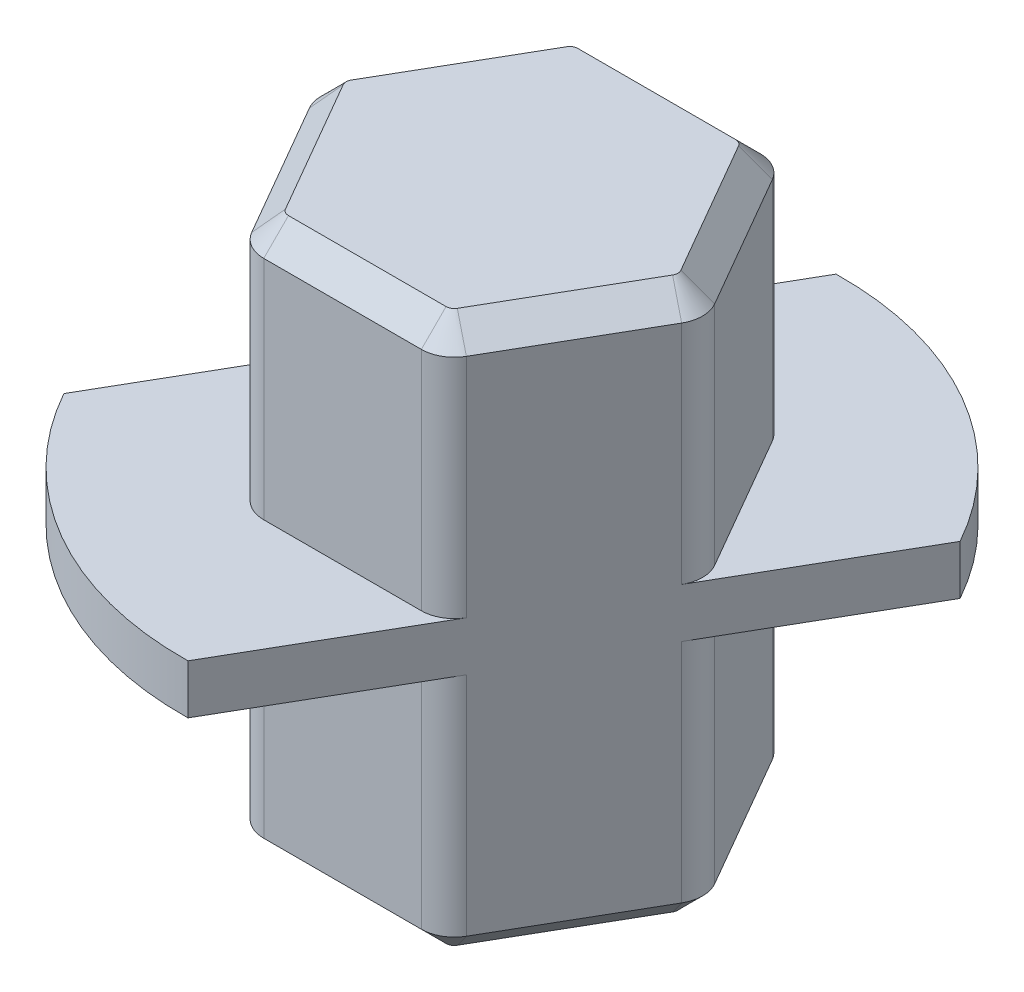
SolidWorks part; units mm, degrees
ref_plane "Front Plane" through (0, 0, 0) normal (0, 0, 1) x (1, 0, 0)
ref_plane "Top Plane" through (0, 0, 0) normal (0, 1, 0) x (1, 0, 0)
ref_plane "Right Plane" through (0, 0, 0) normal (1, 0, 0) x (0, 0, -1)
sketch "Sketch1" plane through (0, 0, 0) normal (0, 1, 0) x (1, 0, 0)
  line L0 (-11.875, 0) -> (11.875, 0) construction
  line L7 (5.9375, 10.2841) -> (-5.9375, 10.2841)
  line L8 (-5.9375, 10.2841) -> (-11.875, 0)
  line L9 (-11.875, 0) -> (-5.9375, -10.2841)
  line L10 (-5.9375, -10.2841) -> (5.9375, -10.2841)
  line L11 (5.9375, -10.2841) -> (11.875, 0)
  line L12 (11.875, 0) -> (5.9375, 10.2841)
  line L13 (-5.9375, -10.2841) -> (5.9375, 10.2841) construction
  circle A0 centre (0, 0) radius 10.2841 construction
  dimension "D1" = 23.75
extrude "Boss-Extrude1" add sketch "Sketch1" along normal blind 15.24
sketch "Sketch2" plane through (0, 15.24, 0) normal (0, 1, 0) x (1, 0, 0)
  circle A0 centre (0, 0) radius 20
  dimension "D1" = 40
extrude "Boss-Extrude2" add sketch "Sketch2" along normal blind 3
extrude "Boss-Extrude3" add sketch "Sketch1<2>" along normal blind 15.24 from surface starting at face at (0, 18.24, 20)
sketch "Sketch1<2>" plane through (0, 0, 0) normal (0, 1, 0) x (1, 0, 0) same geometry as "Sketch1"
fillet "Fillet1" radius 2 12 edges at (5.9375, 7.62, -10.2841) (-5.9375, 7.62, -10.2841) (-11.875, 7.62, 0) (-5.9375, 7.62, 10.2841) (5.9375, 7.62, 10.2841) (11.875, 7.62, 0) (5.9375, 25.86, -10.2841) (-5.9375, 25.86, -10.2841) (-11.875, 25.86, 0) (-5.9375, 25.86, 10.2841) (5.9375, 25.86, 10.2841) (11.875, 25.86, 0)
sketch "Sketch3" plane through (-8.9063, 0, -5.142) normal (-0.866, 0, -0.5) x (-0.5, 0, 0.866)
  line L1 (-17.3683, 33.4435) -> (18.5213, 33.4435)
  line L2 (-17.3683, 33.4435) -> (-17.3683, 12.0694)
  line L3 (-17.3683, 12.0694) -> (18.5213, 12.0694)
  line L4 (18.5213, 33.4435) -> (18.5213, 12.0694)
extrude "Cut-Extrude1" cut sketch "Sketch3" along normal through all
chamfer "Chamfer2" distance 1.5 angle 45 24 edges at (-5.7828, 0, -10.0161) (-8.9062, 0, -5.142) (-11.5656, 0, 0) (-8.9063, 0, 5.142) (-5.7828, 0, 10.0161) (0, 0, 10.2841) (5.7828, 0, 10.0161) (8.9063, 0, 5.142) (11.5656, 0, 0) (8.9063, 0, -5.142) (5.7828, 0, -10.0161) (0, 0, -10.2841) (11.5656, 33.48, 0) (8.9063, 33.48, 5.142) (5.7828, 33.48, 10.0161) (0, 33.48, 10.2841) (-5.7828, 33.48, 10.0161) (-8.9063, 33.48, 5.142) (-11.5656, 33.48, 0) (-8.9063, 33.48, -5.142) (-5.7828, 33.48, -10.0161) (0, 33.48, -10.2841) (5.7828, 33.48, -10.0161) (8.9063, 33.48, -5.142)
sketch "Sketch5" plane through (8.9063, 0, 5.142) normal (0.866, 0, 0.5) x (0.5, 0, -0.866)
  line L1 (-26.761, 28.7725) -> (24.6789, 28.7725)
  line L2 (-26.761, 28.7725) -> (-26.761, 12.8455)
  line L3 (-26.761, 12.8455) -> (24.6789, 12.8455)
  line L4 (24.6789, 28.7725) -> (24.6789, 12.8455)
extrude "Cut-Extrude3" cut sketch "Sketch5" along normal through all
sketch "Sketch4" plane through (0, 33.48, 0) normal (0, 1, 0) x (1, 0, 0)
  line L1 (3.6281, 6.2841) -> (-3.6281, 6.2841)
  line L2 (-3.6281, 6.2841) -> (-7.2562, 0)
  line L3 (-7.2562, 0) -> (-3.6281, -6.2841)
  line L4 (-3.6281, -6.2841) -> (3.6281, -6.2841)
  line L5 (3.6281, -6.2841) -> (7.2562, 0)
  line L6 (7.2562, 0) -> (3.6281, 6.2841)
  line L7 (-4.7828, 10.2841) -> (4.7828, 10.2841) construction
  line L9 (-4.7828, 10.2841) -> (4.7828, 10.2841) construction
  circle A0 centre (0, 0) radius 6.2841 construction
  dimension "D1" = 4
extrude "Cut-Extrude2" [suppressed] cut sketch "Sketch4" against normal through all
